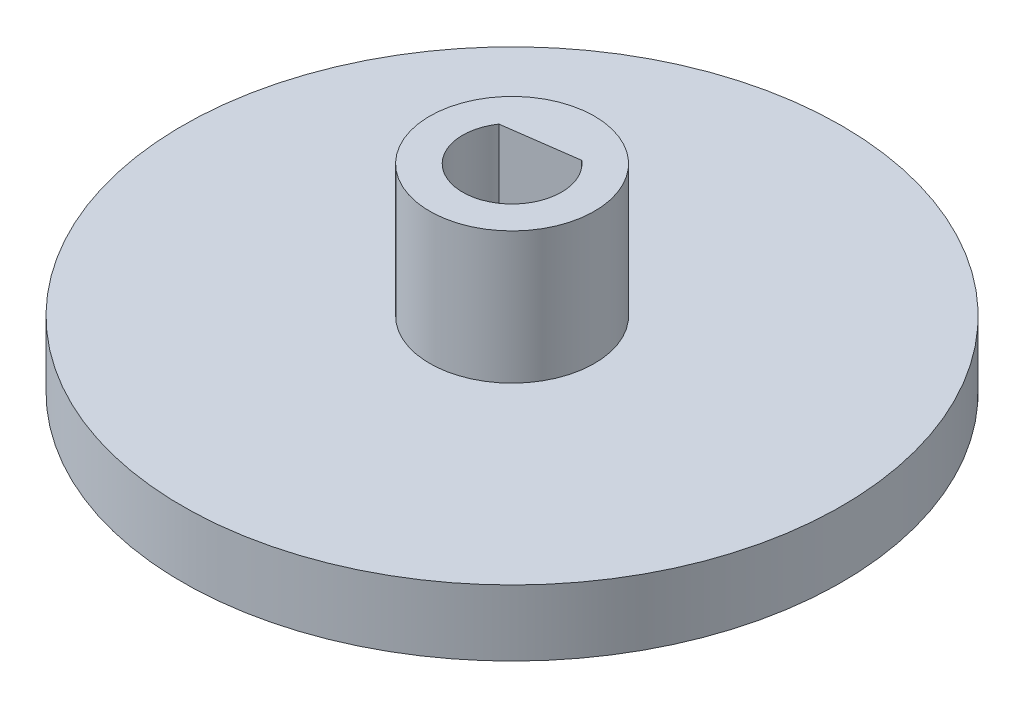
SolidWorks part; units mm, degrees
note: The reader was unsure of these and kept them because the rebuilt part matched: shared geometry of "Sketch4<2>".
ref_plane "Front Plane" through (0, 0, 0) normal (0, 0, 1) x (1, 0, 0)
ref_plane "Top Plane" through (0, 0, 0) normal (0, 1, 0) x (1, 0, 0)
ref_plane "Right Plane" through (0, 0, 0) normal (1, 0, 0) x (0, 0, -1)
sketch "Sketch1" plane through (0, 0, 0) normal (0, 1, 0) x (1, 0, 0)
  line L0 (-1.2424, 0.8404) -> (0.9688, 1.1451)
  line L1 (-1.2424, 0.8404) -> (0.9688, 1.1451)
  circle A0 centre (0, 0) radius 1.5
  arc A1 (0.9688, 1.1451) -> (-1.2424, 0.8404) centre (0, 0) cw
  circle A2 centre (0, 0) radius 2.5
  dimension "D3" = 3
  dimension "D5" = 1
  dimension "D1" = 1.0022
  dimension "D2" = 2.2321
  dimension "D4" = 0.9688
extrude "Boss-Extrude1" add sketch "Sketch1" along normal blind 10
sketch "Sketch3" plane through (0, 10, 0) normal (0, 1, 0) x (1, 0, 0)
  circle A0 centre (0, 0) radius 2.5
  circle A1 centre (0, 0) radius 10
  dimension "D1" = 7.5
extrude "Boss-Extrude2" add sketch "Sketch3" against normal blind 4
sketch "Sketch4" plane through (0, 6, 0) normal (0, -1, 0) x (1, 0, 0)
  circle A0 centre (0, 0) radius 2.5
  circle A1 centre (0, 0) radius 10
extrude "Boss-Extrude3" add sketch "Sketch4" along normal blind 2
extrude "Cut-Extrude1" cut sketch "Sketch4<2>" against normal blind 4
sketch "Sketch4<2>" plane through (0, 6, 0) normal (0, -1, 0) x (1, 0, 0) same geometry as "Sketch4"
